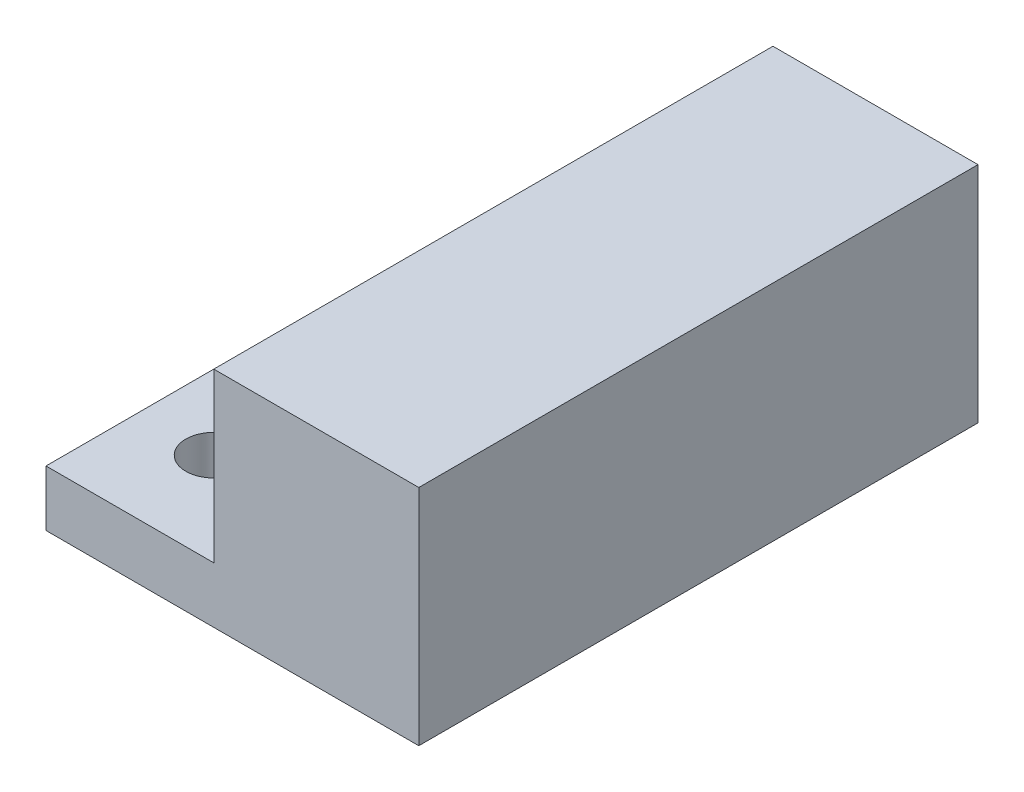
SolidWorks part; units mm, degrees
ref_plane "Front Plane" through (0, 0, 0) normal (0, 0, 1) x (1, 0, 0)
ref_plane "Top Plane" through (0, 0, 0) normal (0, 1, 0) x (1, 0, 0)
ref_plane "Right Plane" through (0, 0, 0) normal (1, 0, 0) x (0, 0, -1)
sketch "Sketch1" plane through (0, 0, 0) normal (0, 1, 0) x (1, 0, 0)
  line L0 (0, 0) -> (0, -25.4) construction
  line L1 (-20.32, 6.35) -> (5.08, 6.35)
  line L2 (-20.32, 6.35) -> (-20.32, -31.75)
  line L3 (-20.32, -31.75) -> (5.08, -31.75)
  line L4 (5.08, 6.35) -> (5.08, -31.75)
  circle A0 centre (0, 0) radius 1.905
  circle A1 centre (0, -25.4) radius 1.905
  point P6 (-20.32, -12.7)
  point P12 (0, -12.7)
  dimension "D1" = 25.4
  dimension "D2" = 3.81
  dimension "D3" = 3.81
  dimension "D4" = 5.08
  dimension "D5" = 38.1
  dimension "D6" = 25.4
extrude "Boss-Extrude1" add sketch "Sketch1" along normal blind 3.81
sketch "Sketch2" plane through (0, 3.81, 0) normal (0, 1, 0) x (1, 0, 0)
  line L0 (-20.32, 6.35) -> (-20.32, -31.75)
  line L1 (-20.32, -31.75) -> (-6.35, -31.75)
  line L2 (-20.32, -31.75) -> (5.08, -31.75) construction
  line L3 (-6.35, -31.75) -> (-6.35, 6.35)
  line L4 (5.08, 6.35) -> (-20.32, 6.35) construction
  line L5 (-6.35, 6.35) -> (-8.89, 6.35)
  line L6 (-8.89, 6.35) -> (-8.89, -29.21)
  line L7 (-8.89, -29.21) -> (-17.78, -29.21)
  line L8 (-17.78, -29.21) -> (-17.78, 6.35)
  line L9 (-17.78, 6.35) -> (-20.32, 6.35)
  dimension "D1" = 2.54
  dimension "D2" = 8.89
  dimension "D3" = 2.54
extrude "Boss-Extrude2" add sketch "Sketch2" along normal blind 8.89 contours L0 L1 L3 L5 L6 L7 L8 L9
sketch "Sketch3" plane through (0, 12.7, 0) normal (0, 1, 0) x (1, 0, 0)
  line L1 (-20.32, 6.35) -> (-6.35, 6.35)
  line L2 (-20.32, 6.35) -> (-20.32, -31.75)
  line L3 (-20.32, -31.75) -> (-6.35, -31.75)
  line L4 (-6.35, 6.35) -> (-6.35, -31.75)
extrude "Boss-Extrude3" add sketch "Sketch3" along normal blind 2.54
chamfer "Chamfer1" distance 1.27 angle 45 2 edges at (-8.89, 12.7, 11.43) (-17.78, 12.7, 11.43)
mirror "Mirror1" about plane through (5.08, 3.81, -6.35) normal (-1, 0, 0) of bodies 103
delete or keep bodies "Body-Delete/Keep 1" type delete bodies bodies 103
